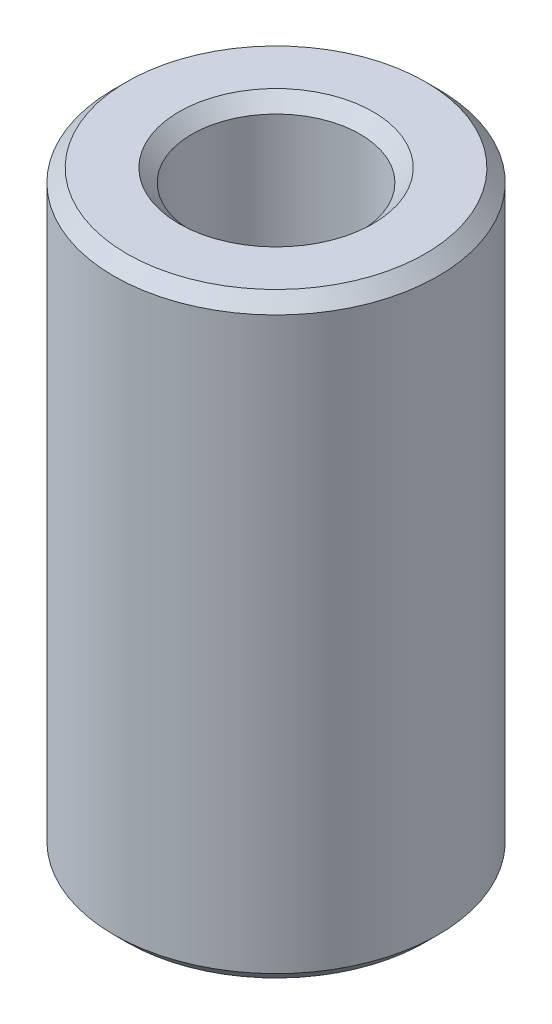
SolidWorks part; units mm, degrees
ref_plane "Front Plane" through (0, 0, 0) normal (0, 0, 1) x (1, 0, 0)
ref_plane "Top Plane" through (0, 0, 0) normal (0, 1, 0) x (1, 0, 0)
ref_plane "Right Plane" through (0, 0, 0) normal (1, 0, 0) x (0, 0, -1)
sketch "Sketch1" plane through (0, 0, 0) normal (0, 1, 0) x (1, 0, 0)
  circle A0 centre (0, 0) radius 50
  dimension "SLEEVE_OD" = 100
extrude "Boss-Extrude1" add sketch "Sketch1" along normal blind 183.9736
sketch "Sketch2" plane through (0, 0, 0) normal (0, 1, 0) x (1, 0, 0)
  circle A0 centre (0, 0) radius 25.946
  dimension "BORE_D" = 51.8919
extrude "Cut-Extrude1" cut sketch "Sketch2" along normal through all
chamfer "Chamfer1" distance 3.9902 angle 45 4 edges at (0, 183.9736, 25.946) (0, 0, 25.946) (0, 0, 50) (0, 183.9736, 50)
